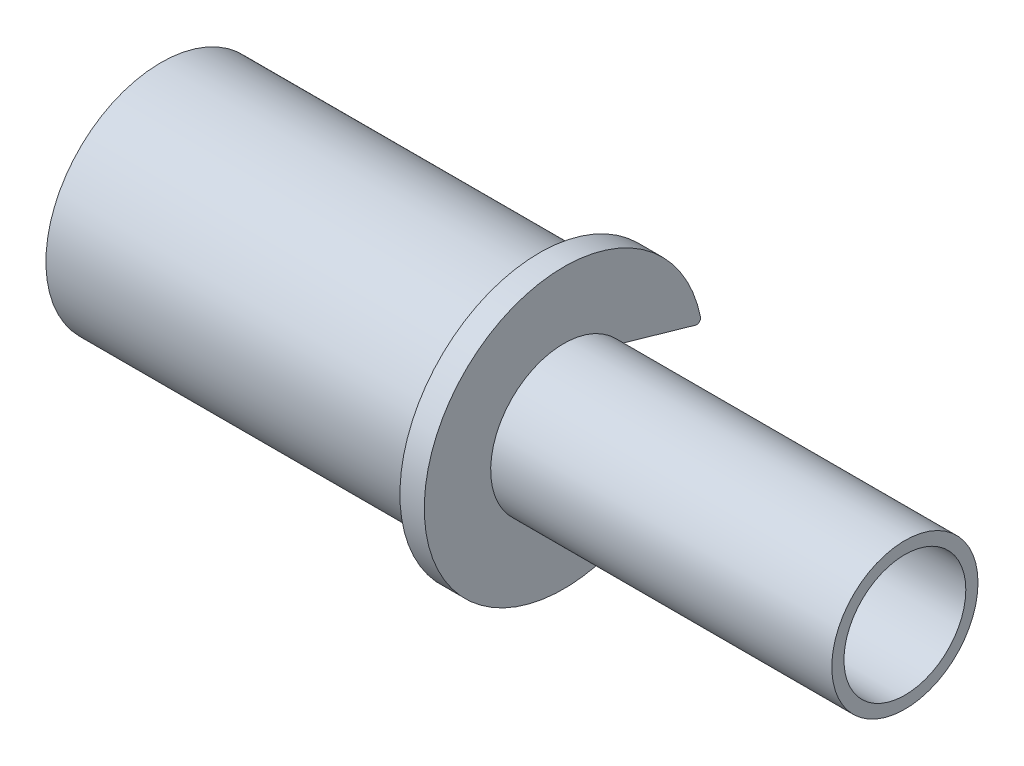
SolidWorks part; units mm, degrees
material "6061-T6 (SS)"
ref_plane "Front Plane" through (0, 0, 0) normal (0, 0, 1) x (1, 0, 0)
ref_plane "Top Plane" through (0, 0, 0) normal (0, 1, 0) x (1, 0, 0)
ref_plane "Right Plane" through (0, 0, 0) normal (1, 0, 0) x (0, 0, -1)
sketch "Sketch1" plane through (0, 0, 0) normal (0, 0, 1) x (1, 0, 0)
  line L0 (0, 0) -> (-16.6687, 0) construction
  line L1 (-3.6156, 3.9687) -> (-3.6156, 4.7625)
  line L2 (-3.6156, 4.7625) -> (-25.8406, 4.7625)
  line L3 (-25.8406, 4.7625) -> (-25.8406, 9.0875)
  line L4 (-25.8406, 9.0875) -> (-27.4281, 9.0875)
  line L5 (-27.4281, 9.0875) -> (-27.4281, 7.5)
  line L6 (-27.4281, 7.5) -> (-52.0781, 7.5)
  line L7 (-52.0781, 7.5) -> (-52.0781, 3.9687)
  line L8 (-52.0781, 3.9687) -> (-3.6156, 3.9687)
  line L11 (-52.0781, -4.2228) -> (-52.0781, 4.2227) construction
  line L12 (-34.4281, 15.2446) -> (-34.4281, -15.2446) construction
  dimension "D1" = 7.9375
  dimension "D4" = 15
  dimension "D3" = 9.525
  dimension "D2" = 1.5875
  dimension "D5" = 1.5875
  dimension "D6" = 7
  dimension "D7" = 22.225
revolve "Revolve1" add sketch "Sketch1" angle 360 about L0
sketch "Sketch4" plane through (-52.0781, 0, 0) normal (-1, 0, 0) x (0, 0, 1)
  line L0 (-2.6253, 9.1561) -> (0, 0) construction
  arc A0 (-10.1862, 9.2089) -> (3.7589, 13.2073) centre (-6.316, 22.0278) ccw construction
ref_plane "Plane1" through (0, 0, 0) normal (0, 0.2756, 0.9613) x (0, -0.9613, 0.2756)
sketch "Sketch2" plane through (-3.6156, 0, 0) normal (1, 0, 0) x (0, 0, -1)
  line L0 (1.3441, 3.7342) -> (8.2848, 3.7342)
  line L1 (8.2848, -3.7342) -> (1.3441, -3.7342)
  line L2 (0, 0) -> (14.3216, 0) construction
  circle A0 centre (0, 0) radius 3.9687 construction
  circle A1 centre (0, 0) radius 9.0875 construction
  arc A2 (1.3441, 3.7342) -> (1.3441, -3.7342) centre (0, 0) cw
  arc A3 (8.2848, 3.7342) -> (8.2848, -3.7342) centre (0, 0) cw
  arc A4 (3.6742, 3.7342) -> (3.6742, -3.7342) centre (0, 0) cw construction
  circle A5 centre (5.2387, 0) radius 1.27 construction
  circle A6 centre (4.623, 2.4642) radius 1.27 construction
  circle A7 centre (4.623, -2.4642) radius 1.27 construction
  dimension "D1" = 1.27
  dimension "D2" = 2.54
extrude "Cut-Extrude1" [suppressed] cut sketch "Sketch2" against normal through all both
sketch "Sketch3" plane through (0, 0, 0) normal (0, 0.2756, 0.9613) x (1, 0, 0)
  line L1 (-39.3781, 1.4287) -> (-39.3781, -1.4287)
  line L2 (-36.9969, -3.81) -> (-25.8406, -3.81)
  line L3 (-39.3781, 8.89) -> (-39.3781, -8.89) construction
  line L4 (-25.8406, 3.81) -> (-36.9969, 3.81)
  line L5 (-22.6656, -0.635) -> (-22.6656, 0.635)
  line L6 (-22.6656, 0) -> (0, 0) construction
  line L7 (-52.0781, 3.81) -> (-52.0781, -3.81)
  line L8 (-25.8406, -9.0875) -> (-25.8406, 9.0875) construction
  line L9 (-52.0781, 7.5) -> (-52.0781, -7.5) construction
  line L10 (-52.0781, -3.81) -> (-48.9031, -3.81)
  line L11 (-47.3156, -2.2225) -> (-47.3156, 2.2225)
  line L12 (-48.9031, 3.81) -> (-52.0781, 3.81)
  arc A1 (-25.8406, -3.81) -> (-22.6656, -0.635) centre (-25.8406, -0.635) ccw
  arc A2 (-22.6656, 0.635) -> (-25.8406, 3.81) centre (-25.8406, 0.635) ccw
  arc A3 (-39.3781, -1.4287) -> (-36.9969, -3.81) centre (-36.9969, -1.4287) ccw
  arc A4 (-39.3781, 1.4287) -> (-36.9969, 3.81) centre (-36.9969, 1.4287) cw
  arc A5 (-48.9031, -3.81) -> (-47.3156, -2.2225) centre (-48.9031, -2.2225) ccw
  arc A6 (-47.3156, 2.2225) -> (-48.9031, 3.81) centre (-48.9031, 2.2225) ccw
  dimension "D1" = 7.62
  dimension "D2" = 3.175
  dimension "D3" = 2.3813
  dimension "D4" = 1.5875
  dimension "D5" = 3.175
extrude "Cut-Extrude2" cut sketch "Sketch3" against normal up to next
fillet "Fillet1" radius 0.254 12 edges at (-26.6344, 1.3885, -8.9808) (-26.6344, -5.9364, -6.8806) (-32.2125, -5.443, -5.1598) (-32.2125, 1.8819, -7.2601) (-38.8575, -4.7066, -5.8393) (-39.3781, -2.0672, -7.2095) (-38.3557, 1.4084, -7.3666) (-50.4906, 1.8819, -7.2601) (-47.6952, 1.264, -7.3927) (-47.3156, -2.0672, -7.2095) (-48.0025, -5.217, -5.3882) (-50.4906, -5.443, -5.1598)
equation "\"bearing1\"=0.273438"
equation "\"D1@Sketch1\"=5/16"
equation "\"D4@Sketch1\"=15mm"
equation "\"D6@Sketch1\"=7mm"
